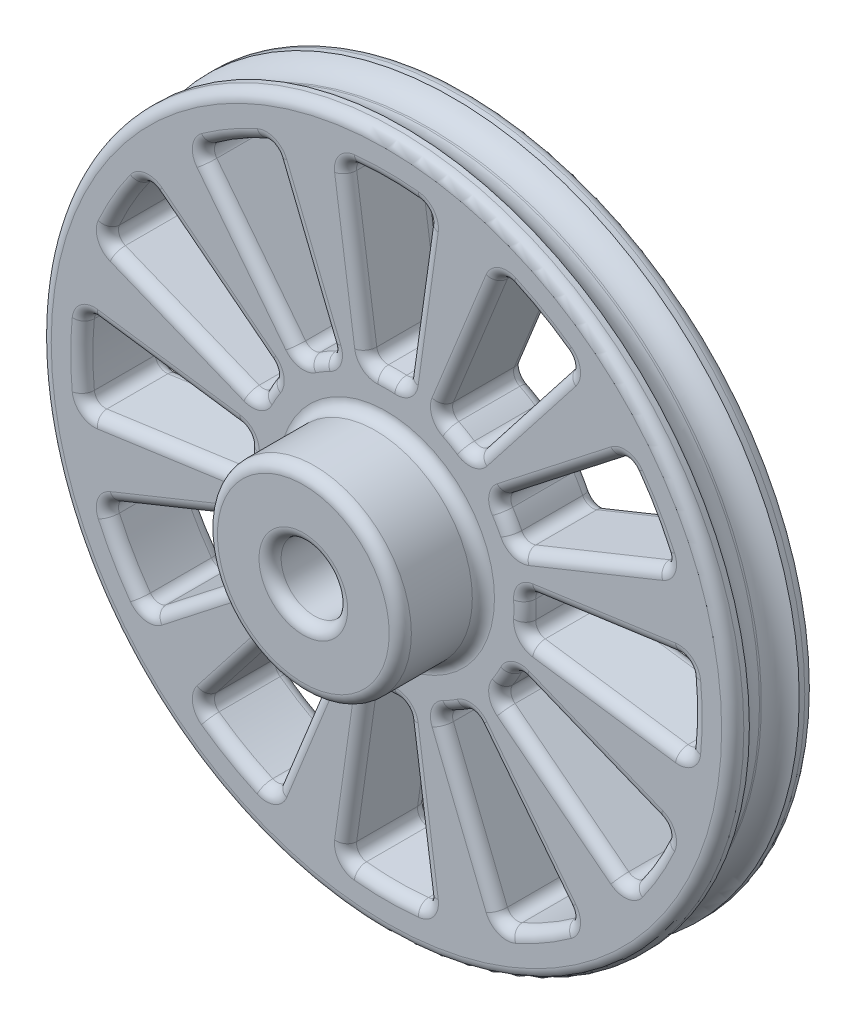
SolidWorks part; units mm, degrees
ref_plane "Front Plane" through (0, 0, 0) normal (0, 0, 1) x (1, 0, 0)
ref_plane "Top Plane" through (0, 0, 0) normal (0, 1, 0) x (1, 0, 0)
ref_plane "Right Plane" through (0, 0, 0) normal (1, 0, 0) x (0, 0, -1)
sketch "Sketch1" plane through (0, 0, 0) normal (0, 0, 1) x (1, 0, 0)
  circle A0 centre (0, 0) radius 12.5
  dimension "D1" = 25
extrude "Boss-Extrude1" add sketch "Sketch1" along normal blind 0.6
sketch "Sketch2" plane through (0, 0, 0.6) normal (0, 0, 1) x (1, 0, 0)
  circle A2 centre (0, 0) radius 12
  circle A3 centre (0, 0) radius 12
  dimension "D1" = 0.5
extrude "Boss-Extrude2" add sketch "Sketch2" along normal blind 1.8
sketch "Sketch3" plane through (0, 0, 2.4) normal (0, 0, 1) x (1, 0, 0)
  circle A2 centre (0, 0) radius 12.5
  circle A3 centre (0, 0) radius 12.5
  dimension "D1" = 0.5
extrude "Boss-Extrude3" add sketch "Sketch3" along normal blind 0.6
sketch "Sketch4" plane through (0, 0, 3) normal (0, 0, 1) x (1, 0, 0)
  circle A0 centre (0, 0) radius 1.2
  dimension "D1" = 2.4
extrude "Cut-Extrude1" cut sketch "Sketch4" against normal blind 10
fillet "Fillet1" radius 1 2 edges at (12, 0, 0.6) (12, 0, 2.4)
sketch "Sketch6" plane through (0, 0, 3) normal (0, 0, 1) x (1, 0, 0)
  line L0 (0, 0) -> (-13.4054, 0) construction
  line L1 (0, 0) -> (-14.1068, -1.9826)
  line L2 (0, 0) -> (-13.2989, 1.869)
  line L3 (0, 0) -> (-10.5827, 8.2681)
  line L4 (0, 0) -> (-13.2081, 5.3364)
  line L5 (0, 0) -> (-5.0308, 12.4517)
  line L6 (0, 0) -> (-8.7704, 11.2255)
  line L7 (0, 0) -> (1.869, 13.2989)
  line L8 (0, 0) -> (-1.9826, 14.1068)
  line L9 (0, 0) -> (8.2681, 10.5827)
  line L10 (0, 0) -> (5.3364, 13.2081)
  line L11 (0, 0) -> (12.4517, 5.0308)
  line L12 (0, 0) -> (11.2255, 8.7704)
  line L13 (0, 0) -> (13.2989, -1.869)
  line L14 (0, 0) -> (14.1068, 1.9826)
  line L15 (0, 0) -> (10.5827, -8.2681)
  line L16 (0, 0) -> (13.2081, -5.3364)
  line L17 (0, 0) -> (5.0308, -12.4517)
  line L18 (0, 0) -> (8.7704, -11.2255)
  line L19 (0, 0) -> (-1.869, -13.2989)
  line L20 (0, 0) -> (1.9826, -14.1068)
  line L21 (0, 0) -> (-8.2681, -10.5827)
  line L22 (0, 0) -> (-5.3364, -13.2081)
  line L23 (0, 0) -> (-12.4517, -5.0308)
  line L24 (0, 0) -> (-11.2255, -8.7704)
  circle A1 centre (0, 0) radius 5
  circle A2 centre (0, 0) radius 11
  circle A3 centre (0, 0) radius 11
  point P29 (0, 0)
  dimension "D1" = 8
  dimension "D2" = 8
  dimension "D3" = 1.5
  dimension "D4" = 6
  dimension "D5" = 12
extrude "Cut-Extrude2" cut sketch "Sketch6" against normal blind 5 contours A1 L0 A3 L1 | L0 A1 L2 A3 | L3 A3 L4 A1 | L5 A3 L6 A1 | L7 A3 L8 A1 | L9 A3 L10 A1 | L11 A3 L12 A1 | L13 A3 L14 A1 | L15 A3 L16 A1 | L17 A3 L18 A1 | L19 A3 L20 A1 | L21 A3 L22 A1 | L23 A3 L24 A1 region at (-8.3478, -0.5837, 3) region at (-8.3478, 0.5837, 3) region at (-7.2294, 4.1739, 3) region at (-4.1739, 7.2294, 3) region at (0, 8.3478, 3) region at (4.1739, 7.2294, 3) region at (7.2294, 4.1739, 3) region at (8.3478, 0, 3) region at (7.2294, -4.1739, 3) region at (4.1739, -7.2294, 3) region at (0, -8.3478, 3) region at (-4.1739, -7.2294, 3) region at (-7.2294, -4.1739, 3)
fillet "Fillet2" radius 0.4 2 edges at (12.5, 0, 3) (12.5, 0, 0)
fillet "Fillet3" radius 0.4 134 edges at (4.3301, -2.5, 0) (9.5263, -5.5, 0) (9.5263, -5.5, 3) (4.3301, -2.5, 3) (2.5, -4.3301, 0) (5.5, -9.5263, 0) (0, -5, 0) (0, -11, 0) (0, -11, 3) (0, -5, 3) (-2.5, -4.3301, 0) (-5.5, -9.5263, 3) (-5.5, -9.5263, 0) (-4.3301, -2.5, 0) (-9.5263, -5.5, 0) (-9.5263, -5.5, 3) (-4.3301, -2.5, 3) (-5, 0, 0) (-5, 0, 3) (-11, 0, 3) (-4.3301, 2.5, 0) (-9.5263, 5.5, 0) (-9.5263, 5.5, 3) (-2.5, 4.3301, 0) (-2.5, 4.3301, 3) (-5.5, 9.5263, 3) (-5.5, 9.5263, 0) (0, 11, 3) (0, 11, 0) (2.5, 4.3301, 0) (5.5, 9.5263, 0) (2.5, 4.3301, 3) (4.3301, 2.5, 0) (9.5263, 5.5, 0) (5, 0, 0) (11, 0, 0) (11, 0, 3) (5, 0, 3) (4.6359, -1.873, 1.5) (7.4175, -2.9969, 3) (10.199, -4.1207, 1.5) (7.4175, -2.9969, 0) (6.3041, -4.9253, 0) (8.6681, -6.7723, 1.5) (6.3041, -4.9253, 3) (3.9401, -3.0783, 1.5) (2.9969, -7.4175, 0) (4.1207, -10.199, 1.5) (2.9969, -7.4175, 3) (1.873, -4.6359, 1.5) (0.6959, -4.9513, 1.5) (1.1134, -7.9221, 3) (1.5309, -10.8929, 1.5) (1.1134, -7.9221, 0) (3.0783, -3.9401, 1.5) (4.9253, -6.3041, 3) (6.7723, -8.6681, 1.5) (4.9253, -6.3041, 0) (-1.1134, -7.9221, 0) (-1.5309, -10.8929, 1.5) (-1.1134, -7.9221, 3) (-0.6959, -4.9513, 1.5) (-4.9253, -6.3041, 0) (-6.7723, -8.6681, 1.5) (-4.9253, -6.3041, 3) (-3.0783, -3.9401, 1.5) (-1.873, -4.6359, 1.5) (-2.9969, -7.4175, 3) (-4.1207, -10.199, 1.5) (-2.9969, -7.4175, 0) (-3.9401, -3.0783, 1.5) (-6.3041, -4.9253, 3) (-8.6681, -6.7723, 1.5) (-6.3041, -4.9253, 0) (-7.4175, -2.9969, 0) (-10.199, -4.1207, 1.5) (-7.4175, -2.9969, 3) (-4.6359, -1.873, 1.5) (-7.9221, 1.1134, 0) (-10.8929, 1.5309, 1.5) (-7.9221, 1.1134, 3) (-4.9513, 0.6959, 1.5) (-4.9513, -0.6959, 1.5) (-7.9221, -1.1134, 3) (-10.8929, -1.5309, 1.5) (-7.9221, -1.1134, 0) (-4.6359, 1.873, 1.5) (-7.4175, 2.9969, 3) (-10.199, 4.1207, 1.5) (-7.4175, 2.9969, 0) (-6.3041, 4.9253, 0) (-8.6681, 6.7723, 1.5) (-6.3041, 4.9253, 3) (-3.9401, 3.0783, 1.5) (-2.9969, 7.4175, 0) (-4.1207, 10.199, 1.5) (-2.9969, 7.4175, 3) (-1.873, 4.6359, 1.5) (-3.0783, 3.9401, 1.5) (-4.9253, 6.3041, 3) (-6.7723, 8.6681, 1.5) (-4.9253, 6.3041, 0) (1.1134, 7.9221, 0) (1.5309, 10.8929, 1.5) (1.1134, 7.9221, 3) (0.6959, 4.9513, 1.5) (-0.6959, 4.9513, 1.5) (-1.1134, 7.9221, 3) (-1.5309, 10.8929, 1.5) (-1.1134, 7.9221, 0) (1.873, 4.6359, 1.5) (2.9969, 7.4175, 3) (4.1207, 10.199, 1.5) (2.9969, 7.4175, 0) (4.9253, 6.3041, 0) (6.7723, 8.6681, 1.5) (4.9253, 6.3041, 3) (3.0783, 3.9401, 1.5) (3.9401, 3.0783, 1.5) (6.3041, 4.9253, 3) (8.6681, 6.7723, 1.5) (6.3041, 4.9253, 0) (7.4175, 2.9969, 0) (10.199, 4.1207, 1.5) (7.4175, 2.9969, 3) (4.6359, 1.873, 1.5) (4.9513, 0.6959, 1.5) (7.9221, 1.1134, 3) (10.8929, 1.5309, 1.5) (7.9221, 1.1134, 0) (7.9221, -1.1134, 0) (10.8929, -1.5309, 1.5) (7.9221, -1.1134, 3) (4.9513, -0.6959, 1.5)
sketch "Sketch7" plane through (0, 0, 3) normal (0, 0, 1) x (1, 0, 0)
  circle A0 centre (0, 0) radius 3.5
  circle A3 centre (0, 0) radius 1.2
  circle A4 centre (0, 0) radius 1.2
  dimension "D1" = 7
  dimension "D2" = 0
extrude "Boss-Extrude4" add sketch "Sketch7" along normal blind 3
fillet "Fillet4" radius 0.4 1 edges at (3.5, 0, 6)
fillet "Fillet5" radius 0.4 1 edges at (1.2, 0, 6)
fillet "Fillet6" radius 0.4 1 edges at (3.5, 0, 3)
fillet "Fillet7" radius 0.4 1 edges at (1.2, 0, 0)
